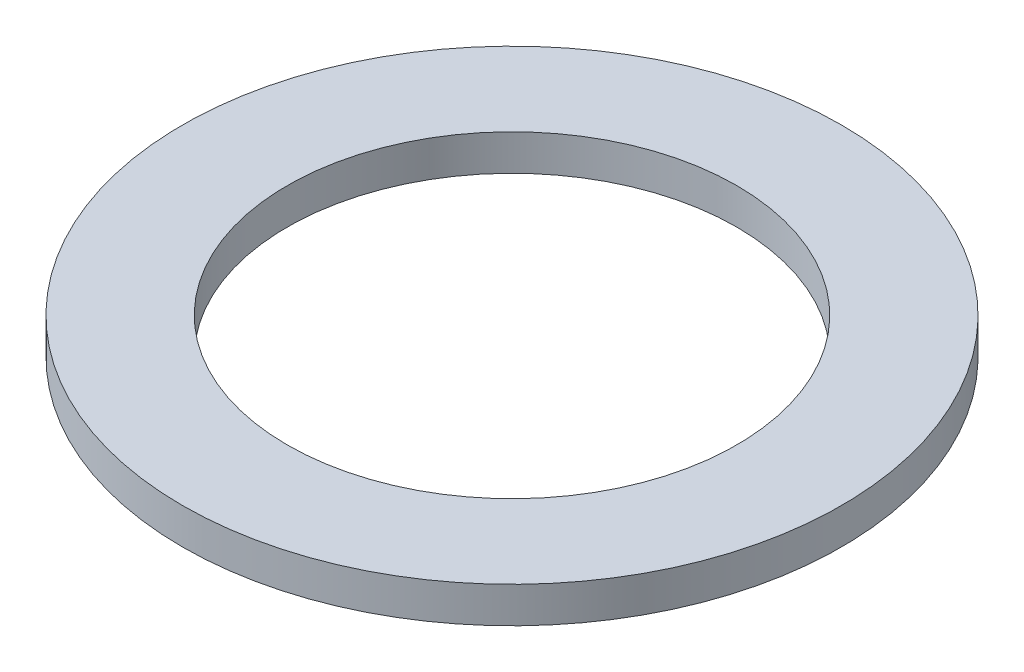
SolidWorks part; units mm, degrees
ref_plane "Front Plane" through (0, 0, 0) normal (0, 0, 1) x (1, 0, 0)
ref_plane "Top Plane" through (0, 0, 0) normal (0, 1, 0) x (1, 0, 0)
ref_plane "Right Plane" through (0, 0, 0) normal (1, 0, 0) x (0, 0, -1)
sketch "Sketch1" plane through (0, 0, 0) normal (0, 1, 0) x (1, 0, 0)
  circle A0 centre (0, 0) radius 55
  dimension "FLANGE_OD" = 110
extrude "Boss-Extrude1" add sketch "Sketch1" along normal blind 6
sketch "Sketch2" plane through (0, 0, 0) normal (0, 1, 0) x (1, 0, 0)
  circle A0 centre (0, 0) radius 37.5
  dimension "BORE_D" = 75
extrude "Cut-Extrude1" cut sketch "Sketch2" along normal through all
sketch "Sketch3" plane through (0, 6, 0) normal (0, 1, 0) x (1, 0, 0)
  circle A0 centre (0, 0) radius 24.9259 construction
  circle A1 centre (-24.9259, 0) radius 2.5843
  dimension "BOLT_D" = 5.1685
  dimension "BOLT_PCD" = 49.8517
extrude "Cut-Extrude2" cut sketch "Sketch3" against normal blind 5.3187 rebuild error yes
pattern_circular "CirPattern1" count 8 over 360 rebuild error yes
